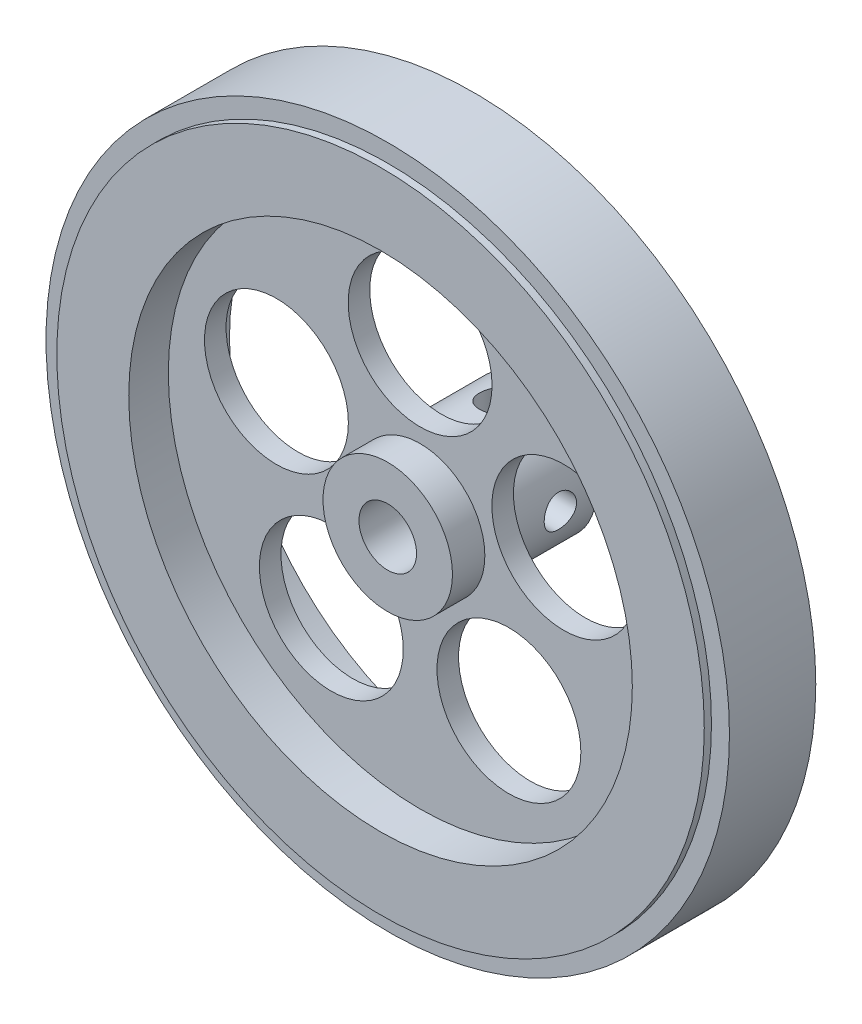
SolidWorks part; units mm, degrees
ref_plane "정면" through (0, 0, 0) normal (0, 0, 1) x (1, 0, 0)
ref_plane "윗면" through (0, 0, 0) normal (0, 1, 0) x (1, 0, 0)
ref_plane "우측면" through (0, 0, 0) normal (1, 0, 0) x (0, 0, -1)
sketch "스케치1" plane through (0, 0, 0) normal (0, 0, 1) x (1, 0, 0)
  circle A0 centre (0, 0) radius 4
  circle A1 centre (0, 0) radius 9
  dimension "D1" = 8
  dimension "D2" = 18
extrude "보스-돌출1" add sketch "스케치1" along normal blind 20
ref_plane "평면1" through (0, 0, 14) normal (0, 0, 1) x (1, 0, 0)
sketch "스케치2" plane through (0, 0, 14) normal (0, 0, 1) x (1, 0, 0)
  circle A0 centre (0, 0) radius 45
  dimension "D1" = 90
extrude "보스-돌출2" add sketch "스케치2" along normal blind 1.5 and the other way blind 1.5
extrude "컷-돌출2" cut sketch "스케치1<2>" along normal through all both and the other way through all contours A0 region at (0, 0, 0)
sketch "스케치1<2>" plane through (0, 0, 0) normal (0, 0, 1) x (1, 0, 0) same geometry as "스케치1"
sketch "스케치3" plane through (0, 0, 15.5) normal (0, 0, 1) x (1, 0, 0)
  circle A0 centre (0, 21) radius 10
  circle A1 centre (19.9722, 6.4894) radius 10
  circle A2 centre (12.3435, -16.9894) radius 10
  circle A3 centre (-12.3435, -16.9894) radius 10
  circle A4 centre (-19.9722, 6.4894) radius 10
  point P13 (0, 0)
  dimension "D1" = 20
  dimension "D2" = 21
  dimension "D3" = 5
extrude "컷-돌출3" cut sketch "스케치3" against normal through all both
sketch "스케치5" plane through (0, 0, 14) normal (0, 0, 1) x (1, 0, 0)
  circle A0 centre (0, 0) radius 45
  circle A1 centre (0, 0) radius 35
  dimension "D1" = 10
extrude "보스-돌출3" add sketch "스케치5" along normal blind 7 and the other way blind 7
sketch "스케치6" plane through (0, 0, 14) normal (0, 0, 1) x (1, 0, 0)
  circle A0 centre (0, 0) radius 45
  circle A1 centre (0, 0) radius 47.5
  dimension "D1" = 95
extrude "보스-돌출4" add sketch "스케치6" along normal blind 6 and the other way blind 6
hole_wizard "M4 여유 구멍1" positions "스케치8" profile "스케치9" hole size "M4" standard "HASCO Metric"
sketch "스케치8" plane through (0, 0, 0) normal (0, 1, 0) x (1, 0, 0)
  line L0 (9, 0) -> (-9, 0) construction
  point P0 (0, -5)
  point P3 (0, -6.2172)
  point P4 (0, 0)
  dimension "D1" = 5
sketch "스케치9" plane through (0, 0, 5) normal (1, 0, 0) x (0, 0, -1)
  line L0 (0, 0) -> (0, 31.3519)
  line L1 (0, 31.3519) -> (2.25, 30)
  line L2 (2.25, 30) -> (2.25, 0)
  line L5 (2.25, 0) -> (0, 0)
  line L10 (0, 31.3519) -> (-2.25, 30) construction
  line L11 (0, -6.35) -> (0, 107.95) construction
  dimension "구멍 지름" = 4.5
  dimension "구멍 깊이" = 30
  dimension "드릴 각도" = 118
hole_wizard "M4 여유 구멍2" positions "스케치11" profile "스케치12" hole size "M4" standard "HASCO Metric"
sketch "스케치11" plane through (0, 0, 0) normal (1, 0, 0) x (0, 0, -1)
  line L0 (0, -4) -> (0, 4) construction
  point P0 (-5, 0)
  dimension "D1" = 5
sketch "스케치12" plane through (0, 0, 5) normal (0, 1, 0) x (0, 0, 1)
  line L0 (0, 0) -> (0, 31.3519)
  line L1 (0, 31.3519) -> (2.25, 30)
  line L2 (2.25, 30) -> (2.25, 0)
  line L5 (2.25, 0) -> (0, 0)
  line L10 (0, 31.3519) -> (-2.25, 30) construction
  line L11 (0, -6.35) -> (0, 107.95) construction
  dimension "구멍 지름" = 4.5
  dimension "구멍 깊이" = 30
  dimension "드릴 각도" = 118
